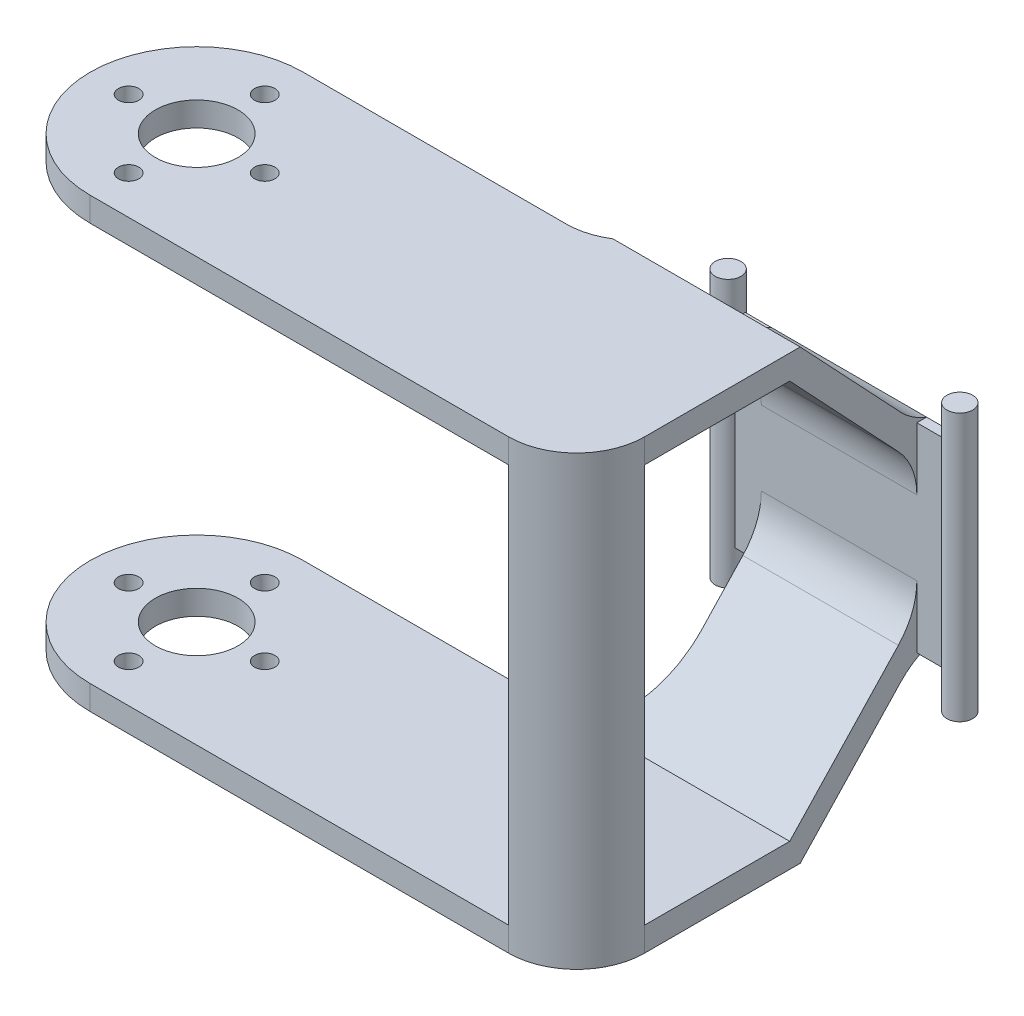
SolidWorks part; units mm, degrees
ref_plane "Front Plane" through (0, 0, 0) normal (0, 0, 1) x (1, 0, 0)
ref_plane "Top Plane" through (0, 0, 0) normal (0, 1, 0) x (1, 0, 0)
ref_plane "Right Plane" through (0, 0, 0) normal (1, 0, 0) x (0, 0, -1)
sketch "Sketch1" plane through (0, 0, 0) normal (0, 1, 0) x (1, 0, 0)
  line L1 (11.915, 0.5) -> (-11.915, 0.5)
  line L2 (11.915, 0.5) -> (11.915, -0.5)
  line L3 (11.915, -0.5) -> (-11.915, -0.5)
  line L4 (-11.915, 0.5) -> (-11.915, -0.5)
  line L5 (11.915, 0.5) -> (-11.915, -0.5) construction
  line L6 (11.915, -0.5) -> (-11.915, 0.5) construction
  point P0 (0, 0)
  dimension "D1" = 23.83
  dimension "D3" = 1
extrude "Boss-Extrude1" add sketch "Sketch1" along normal blind 20.5
ref_plane "Plane1" through (0, 10.25, 0) normal (0, 1, 0) x (1, 0, 0)
sketch "Sketch2" plane through (0, 10.25, 0) normal (0, 1, 0) x (1, 0, 0)
  line L0 (11.915, -0.5) -> (11.915, 0.5) construction
  line L1 (-11.915, 0.5) -> (-11.915, -0.5) construction
  line L2 (11.915, -0.5) -> (11.915, 0.5) construction
  line L3 (-11.915, 0.5) -> (-11.915, -0.5) construction
  circle A0 centre (-11.915, 0) radius 1.325
  circle A1 centre (11.915, 0) radius 1.325
  dimension "D1" = 2.65
extrude "Boss-Extrude2" add sketch "Sketch2" along normal mid plane 27.5
sketch "Sketch3" plane through (0, 20.5, 0) normal (0, 1, 0) x (1, 0, 0)
  line L0 (-10.688, -0.5) -> (10.688, -0.5) construction
  line L1 (-7.5, -0.5) -> (7.5, -0.5)
  line L2 (-7.5, -0.5) -> (-7.5, -26.5)
  line L3 (-7.5, -26.5) -> (7.5, -26.5)
  line L4 (7.5, -0.5) -> (7.5, -26.5)
  line L5 (0, -1000) -> (0, 49000) construction
  line L6 (-7.5, -26.5) -> (-32.5, -26.5)
  line L7 (-7.5, -26.5) -> (-7.5, -3.5)
  line L8 (-7.5, -3.5) -> (-32.5, -3.5)
  line L9 (-32.5, -26.5) -> (-32.5, -3.5)
  line L11 (-4.5, -3.5) -> (4.5, -3.5)
  line L12 (4.5, -3.5) -> (4.5, -23.5)
  line L13 (-4.5, -23.5) -> (4.5, -23.5)
  line L14 (-10.5, -23.5) -> (-29.5, -23.5)
  line L16 (-10.5, -6.5) -> (-29.5, -6.5)
  line L18 (-29.5, -23.5) -> (-29.5, -6.5) construction
  line L19 (-10.5, -23.5) -> (-10.5, -6.5) construction
  line L20 (-4.5, -3.5) -> (-4.5, -23.5) construction
  line L21 (-4.5, -3.5) -> (-4.5, -6.5)
  line L22 (-4.5, -6.5) -> (-10.5, -6.5)
  line L23 (-4.5, -23.5) -> (-10.5, -23.5)
  line L24 (-18.5, -6.5) -> (-18.5, -23.5)
  circle A0 centre (-32.5, -15) radius 11.5
  circle A1 centre (-32.5, -15) radius 4.25
  circle A2 centre (-32.5, -15) radius 7 construction
  circle A3 centre (-32.5, -8) radius 1.05
  circle A4 centre (-25.5, -15) radius 1.05
  circle A5 centre (-32.5, -22) radius 1.05
  circle A6 centre (-39.5, -15) radius 1.05
  point P10 (0, -0.5)
  line M14 (-10.688, -0.5) -> (10.688, -0.5)
  dimension "D5" = 8.5
  dimension "D6" = 14
  dimension "D7" = 2.1
  dimension "D1" = 15
  dimension "D2" = 26
  dimension "D3" = 23
  dimension "D4" = 25
  dimension "D9" = 14
  dimension "D8" = 3
extrude "Boss-Extrude3" [suppressed] add sketch "Sketch3" against normal up to surface (18.5 mm away) contours L4 L2 L3 M14 | A0 L6 L2 L8 | A5 L9 A0 A3 A1 A4 | A5 L9 A1 A3 A0 A6 | A0 L16 L22 L2 L8 | A0 L6 L2 L23 L14
sketch "Sketch4" plane through (0, 0, 0) normal (1, 0, 0) x (0, 0, -1)
  line L0 (-0.5, 20.5) -> (-12.5, 33.25)
  line L1 (-12.5, 33.25) -> (-35.5, 33.25)
  line L2 (-35.5, 33.25) -> (-35.5, 30.75)
  line L3 (-35.5, 30.75) -> (-13.5802, 30.75)
  line L4 (-13.5802, 30.75) -> (-0.5, 16.8523)
  line L5 (-0.5, 20.5) -> (-0.5, 0) construction
  line L6 (-0.5, 20.5) -> (-0.5, 0)
  line L7 (-0.5, 0) -> (-12.5, -12.75)
  line L8 (-12.5, -12.75) -> (-35.5, -12.75)
  line L9 (-35.5, -12.75) -> (-35.5, -10.25)
  line L10 (-35.5, -10.25) -> (-13.5802, -10.25)
  line L11 (-13.5802, -10.25) -> (-0.5, 3.6477)
  line L12 (-1000.5, 10.25) -> (48999.5, 10.25) construction
  line L13 (-35.5, 30.75) -> (-35.5, -10.25) construction
  point P3 (-35.5, 10.25)
  point P18 (0, 0)
  point P20 (-0.5, 10.25)
  point P21 (0, 0)
  dimension "D1" = 2.5
  dimension "D2" = 41
  dimension "D3" = 23
  dimension "D4" = 2.5
  dimension "D5" = 35
  dimension "D6" = 2.5
extrude "Boss-Extrude4" add sketch "Sketch4" along normal mid plane 16 contours L6 L0 L1 L2 L3 L4 | L11 L10 L9 L8 L7 L6
sketch "Sketch5" plane through (-8, 0, 0) normal (-1, 0, 0) x (0, 0, 1)
  line L1 (35.5, 33.25) -> (13.5802, 33.25)
  line L2 (35.5, 33.25) -> (35.5, 30.75)
  line L3 (35.5, 30.75) -> (13.5802, 30.75)
  line L4 (13.5802, 33.25) -> (13.5802, 30.75)
  line L5 (35.5, -12.75) -> (13.5802, -12.75)
  line L6 (35.5, -12.75) -> (35.5, -10.25)
  line L7 (35.5, -10.25) -> (13.5802, -10.25)
  line L8 (13.5802, -12.75) -> (13.5802, -10.25)
extrude "Boss-Extrude5" add sketch "Sketch5" along normal blind 45
sketch "Sketch6" plane through (0, 33.25, 0) normal (0, 1, 0) x (1, 0, 0)
  line L0 (-42.0401, -13.5802) -> (-42.0401, -35.5) construction
  line L1 (-53, -13.5802) -> (-8, -13.5802) construction
  line L2 (8, -35.5) -> (-53, -35.5) construction
  line L3 (-53, -24.5401) -> (8, -24.5401) construction
  line L4 (-53, -35.5) -> (-53, -13.5802) construction
  line L5 (8, -12.5) -> (8, -35.5) construction
  line L6 (-42.0401, -13.5802) -> (-53, -13.5802)
  line L7 (-53, -13.5802) -> (-53, -35.5)
  line L8 (-53, -35.5) -> (-42.0401, -35.5)
  circle A0 centre (-42.0401, -24.5401) radius 10.9599
  circle A1 centre (-42.0401, -24.5401) radius 4.25
  circle A2 centre (-42.0401, -24.5401) radius 7 construction
  circle A3 centre (-42.0401, -17.5401) radius 1.05
  circle A4 centre (-35.0401, -24.5401) radius 1.05
  circle A5 centre (-42.0401, -31.5401) radius 1.05
  circle A6 centre (-49.0401, -24.5401) radius 1.05
  point P12 (-42.0401, -24.5401)
  line M9 (-8, -13.5802) -> (-53, -13.5802)
  line M10 (-53, -13.5802) -> (-53, -35.5)
  line M11 (-53, -35.5) -> (8, -35.5)
  dimension "D1" = 8.5
  dimension "D2" = 14
  dimension "D3" = 2.1
extrude "Cut-Extrude1" cut sketch "Sketch6" against normal through all contours A1 | A6 | A3 | A4 | A5 | A0 M9 M10 | A0 L7 M11
fillet "Fillet1" radius 7 4 edges at (-8, -11.5, 13.5802) (-8, 32, 13.5802) (8, -11.5, 35.5) (8, 32, 35.5)
fillet "Fillet2" radius 7 2 edges at (0, 3.6477, 0.5) (0, 16.8523, 0.5)
fillet "Fillet3" radius 7 2 edges at (0, 20.5, 0.5) (0, 0, 0.5)
sketch "Sketch8" plane through (0, -10.25, 0) normal (0, 1, 0) x (1, 0, 0)
  line L0 (-42.0401, -13.5802) -> (-15, -13.5802) construction
  line L1 (-42.0401, -13.5802) -> (-15, -13.5802)
  line L2 (8, -28.5) -> (5, -28.5)
  line L3 (1, -35.5) -> (1, -32.5)
  arc A0 (-15, -13.5802) -> (-8, -6.5802) centre (-15, -6.5802) ccw construction
  arc A1 (1, -35.5) -> (8, -28.5) centre (1, -28.5) ccw construction
  arc A2 (-15, -13.5802) -> (-8, -6.5802) centre (-15, -6.5802) ccw
  arc A3 (1, -35.5) -> (8, -28.5) centre (1, -28.5) ccw
  circle A4 centre (-1.5277, -25.9723) radius 7
  point P9 (-2.0949, -26.0161)
  point P12 (-0.8902, -26.6098)
  arc M10 (1, -35.5) -> (8, -28.5) centre (1, -28.5) ccw
  dimension "D1" = 3
extrude "Boss-Extrude6" add sketch "Sketch8" along normal up to surface (41 mm away) contours A4 L3 L2 M10 up to face at (-42.0401, 30.75, 28.7901)
equation "\"D4@Sketch4\"=\"D1@Sketch4\""
equation "\"D6@Sketch4\"=\"D1@Sketch4\""
